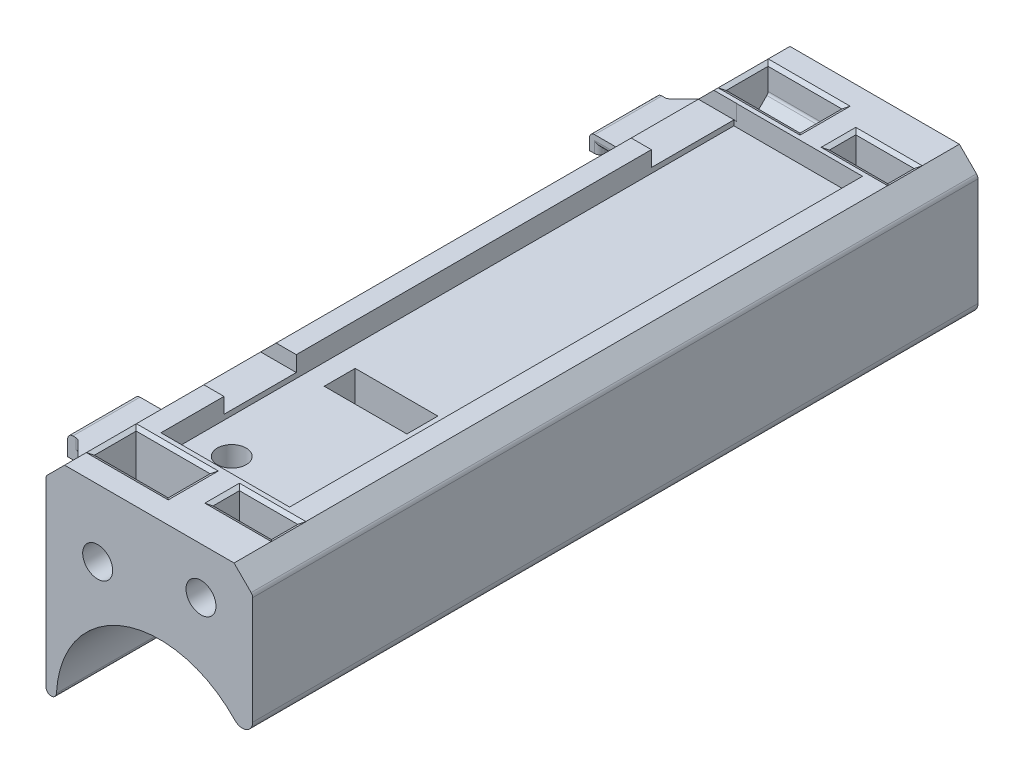
SolidWorks part; units mm, degrees
ref_plane "Front Plane" through (0, 0, 0) normal (0, 0, 1) x (1, 0, 0)
ref_plane "Top Plane" through (0, 0, 0) normal (0, 1, 0) x (1, 0, 0)
ref_plane "Right Plane" through (0, 0, 0) normal (1, 0, 0) x (0, 0, -1)
sketch "Sketch1" plane through (0, 0, 0) normal (0, 0, 1) x (1, 0, 0)
  line L0 (11, 20) -> (11, 10) construction
  line L1 (0, 0) -> (1, 0)
  line L2 (0, 0) -> (0, 20)
  line L3 (0, 20) -> (20, 20)
  line L4 (20, 4.3589) -> (20, 20)
  arc A0 (20, 4.3589) -> (1, 0) centre (11, 0) ccw
extrude "Boss-Extrude2" add sketch "Sketch1" along normal blind 35.1
sketch "Sketch2" plane through (0, 0, 0) normal (-1, 0, 0) x (0, 0, 1)
  line L0 (0, 0) -> (0, 6)
  line L1 (0, 20) -> (0, 0) construction
  line L2 (0, 6) -> (6, 6)
  line L3 (0, 0) -> (17, 0)
  line L4 (35.1, 0) -> (0, 0) construction
  line L5 (6, 6) -> (17, 0)
extrude "Cut-Extrude2" cut sketch "Sketch2" against normal blind 23.1
chamfer "Chamfer1" distance 1.8 angle 45 2 edges at (20, 20, 17.55) (0, 20, 17.55)
fillet "Fillet1" radius 20 2 edges at (0.5, 0, 17) (1.5, 6, 6)
fillet "Fillet3" radius 1 1 edges at (20, 4.3589, 22.0543)
fillet "Fillet2" radius 0.5 12 edges at (0, 18.2, 17.55) (20, 18.2, 17.55) (3, 6, 0.4501) (2.8157, 5.7461, 4.077) (1.4622, 3.0051, 11.4906) (1.0631, 1.1219, 15.4955) (1, 0, 28.5999) (0, 0, 28.5999) (0, 0.6201, 17.1581) (0, 3, 11.5) (0, 5.3799, 5.8419) (0, 6, 0.4501)
sketch "Hole Positions" plane through (0, 0, 35.1) normal (0, 0, 1) x (1, 0, 0)
  line L0 (5, 15.5) -> (11, 15.5) construction
  line L1 (11, 15.5) -> (15, 15.5) construction
  line L2 (11, 15.5) -> (11, 0) construction
  line L3 (5, 15.5) -> (5, 13.5) construction
  circle A2 centre (5, 13.5) radius 1.45
  circle A3 centre (15, 15.5) radius 1.45
  dimension "D1" = 6
  dimension "D2" = 4
  dimension "D3" = 2
  dimension "D4" = 15.5
extrude "Cut-Extrude3" cut sketch "Hole Positions" against normal blind 19
sketch "Sketch3" plane through (0, 20, 0) normal (0, 1, 0) x (1, 0, 0)
  line L1 (2.18, -28.55) -> (7.83, -28.55)
  line L2 (2.18, -28.55) -> (2.18, -31.1)
  line L3 (2.18, -31.1) -> (7.83, -31.1)
  line L4 (7.83, -28.55) -> (7.83, -31.1)
  line L5 (12.17, -28.55) -> (17.82, -28.55)
  line L6 (12.17, -28.55) -> (12.17, -31.1)
  line L7 (12.17, -31.1) -> (17.82, -31.1)
  line L8 (17.82, -28.55) -> (17.82, -31.1)
extrude "Cut-Extrude4" cut sketch "Sketch3" against normal blind 7.9
sketch "Sketch4" plane through (0, 20, 0) normal (0, 1, 0) x (1, 0, 0)
  line L1 (2.18, -31.1) -> (7.83, -31.1)
  line L2 (2.18, -31.1) -> (2.18, -28.55)
  line L3 (2.18, -28.55) -> (7.83, -28.55)
  line L4 (7.83, -31.1) -> (7.83, -28.55)
extrude "Cut-Extrude5" cut sketch "Sketch4" against normal blind 9.9
sketch "Sketch5" plane through (0, 20, 0) normal (0, 1, 0) x (1, 0, 0)
  line L1 (2.18, -28.55) -> (9.33, -28.55)
  line L2 (2.18, -28.55) -> (2.18, -32.6)
  line L3 (2.18, -32.6) -> (9.33, -32.6)
  line L4 (9.33, -28.55) -> (9.33, -32.6)
extrude "Cut-Extrude6" cut sketch "Sketch5" against normal blind 4
chamfer "Chamfer2" distance 2.6 angle 30 4 edges at (2.18, 10.1, 29.825) (7.83, 10.1, 29.825) (12.17, 12.1, 29.825) (17.82, 12.1, 29.825)
chamfer "Chamfer3" distance 1.5 angle 45 3 edges at (5.755, 16, 32.6) (9.33, 16, 30.575) (8.58, 16, 28.55)
chamfer "Chamfer4" distance 0.4 angle 30 8 edges at (14.995, 20, 31.1) (17.82, 20, 29.825) (14.995, 20, 28.55) (12.17, 20, 29.825) (9.33, 20, 30.575) (5.755, 20, 32.6) (2.18, 20, 30.575) (5.755, 20, 28.55)
fillet "Fillet5" radius 0.4 8 edges at (5.755, 17.5, 32.6) (9.33, 17.5, 30.575) (4.78, 10.1, 29.825) (5.23, 10.1, 29.825) (5.005, 16, 31.1) (7.83, 16, 29.825) (14.77, 12.1, 29.825) (15.22, 12.1, 29.825)
sketch "Sketch13" plane through (0, 0, 0) normal (0, 0, 1) x (1, 0, 0)
  line L0 (5, 13.5) -> (0, 13.5) construction
  line L1 (0, 17.9929) -> (0, 0.5) construction
  line L3 (0, 15.25) -> (-3.5, 15.25)
  line L4 (-3.5, 15.25) -> (-3.5, 11.75)
  line L6 (-3.5, 11.75) -> (0, 11.75)
  line L7 (0, 11.75) -> (0, 10.75)
  line L8 (0, 10.75) -> (-3.5, 10.75)
  line L10 (0, 15.25) -> (0, 16.25)
  line L11 (0, 16.25) -> (-3.5, 16.25)
  line L13 (-3.5, 10.75) -> (-4.5, 10.75)
  line L14 (-4.5, 10.75) -> (-4.5, 16.25)
  line L15 (-4.5, 16.25) -> (-3.5, 16.25)
extrude "Boss-Extrude3" add sketch "Sketch13" along normal blind 10 from offset 22
sketch "Sketch14" plane through (0, 10.75, 0) normal (0, -1, 0) x (1, 0, 0)
  line L5 (0, 32) -> (-3.5, 28.5)
  line L6 (-3.5, 28.5) -> (-4.5, 28.5)
  line L7 (-4.5, 32) -> (-4.5, 22) construction
  line L9 (-4.5, 28.5) -> (-4.5, 32)
  line L10 (-4.5, 32) -> (0, 32)
  dimension "D1" = 1
  dimension "D2" = 45
extrude "Cut-Extrude11" cut sketch "Sketch14" against normal blind 6
sketch "Sketch15" plane through (-4.5, 0, 0) normal (-1, 0, 0) x (0, 0, 1)
  line L12 (28.5, 13.5) -> (28.5, 14.25)
  line L13 (28.5, 16.25) -> (28.5, 10.75) construction
  line L14 (28.5, 13.5) -> (28.5, 12.75)
  line L15 (28.5, 14.25) -> (25.5, 14.25)
  line L16 (25.5, 12.75) -> (28.5, 12.75)
  line L17 (25.5, 14.25) -> (24.3724, 14.6604)
  line L18 (25.5, 12.75) -> (24.3724, 13.1604)
  line L19 (24.3724, 14.6604) -> (22, 14.6604)
  line L20 (22, 16.25) -> (22, 10.75) construction
  line L21 (22, 14.6604) -> (22, 13.1604)
  line L22 (22, 13.1604) -> (24.3724, 13.1604)
  dimension "D1" = 0.75
  dimension "D2" = 0.75
  dimension "D3" = 3
  dimension "D4" = 1.2
  dimension "D5" = 1.2
  dimension "D6" = 160
  dimension "D7" = 160
  dimension "3mm" = 3
extrude "Cut-Extrude12" cut sketch "Sketch15" against normal blind 1
fillet "Fillet6" radius 0.5 2 edges at (0, 16.25, 27) (0, 10.75, 27)
fillet "Fillet8" radius 0.5 8 edges at (-4.5, 16.25, 25.25) (-4.5, 10.75, 25.25) (-3.5, 11.25, 28.5) (-3.5, 15.75, 28.5) (-3.5, 14.9552, 22) (-1.75, 15.25, 22) (-3.5, 12.4552, 22) (-1.75, 11.75, 22)
mirror "Mirror1" about plane through (11, 0, 0) normal (0, 0, 1) of bodies 116 108
sketch "Sketch8" plane through (0, 20, 0) normal (0, 1, 0) x (1, 0, 0)
  line L0 (18.2, -28.15) -> (18.2, 28.15) construction
  line L1 (3.75, 27.725) -> (16.2, 27.725)
  line L2 (3.75, 27.725) -> (3.75, -27.725)
  line L3 (3.75, -27.725) -> (16.2, -27.725)
  line L4 (16.2, 27.725) -> (16.2, -27.725)
  line L6 (1.8, 28.15) -> (9.73, 28.15) construction
  dimension "D1" = 2
  dimension "D2" = 12.45
  dimension "D3" = 55.45
  dimension "D4" = 0.425
extrude "Cut-Extrude8" cut sketch "Sketch8" against normal blind 2 contours L2 L1 L4 L3
sketch "Sketch10" plane through (0, 0, 0) normal (-1, 0, 0) x (0, 0, 1)
  line L0 (-28.15, 20) -> (28.15, 20) construction
  line L1 (-27.7377, 20) -> (-19.7377, 20)
  line L2 (-27.7377, 20) -> (-27.7377, 18.5)
  line L3 (-27.7377, 18.5) -> (-19.7377, 18.5)
  line L4 (-19.7377, 20) -> (-19.7377, 18.5)
  line L6 (21.625, 20) -> (14.625, 20)
  line L7 (21.625, 20) -> (21.625, 18.5)
  line L8 (21.625, 18.5) -> (14.625, 18.5)
  line L9 (14.625, 20) -> (14.625, 18.5)
  dimension "D1" = 0.425
  dimension "D2" = 8
  dimension "D3" = 1.5
  dimension "D4" = 7
  dimension "D5" = 1.5
  dimension "D6" = 6.1
extrude "Cut-Extrude9" cut sketch "Sketch10" against normal blind 4
sketch "Sketch11" plane through (0, 18, 0) normal (0, 1, 0) x (1, 0, 0)
  line L0 (3.75, -27.725) -> (16.2, -27.725) construction
  line L1 (5.75, -10.925) -> (13.75, -10.925)
  line L2 (5.75, -10.925) -> (5.75, -13.925)
  line L3 (5.75, -13.925) -> (13.75, -13.925)
  line L4 (13.75, -10.925) -> (13.75, -13.925)
  line L5 (3.75, 27.725) -> (3.75, -27.725) construction
  line L6 (3.75, -21.625) -> (3.75, -27.725) construction
  circle A0 centre (7.15, -24.275) radius 1.4
  dimension "D1" = 2.8
  dimension "D2" = 3
  dimension "D3" = 8
  dimension "D4" = 3.45
  dimension "D5" = 13.8
  dimension "D6" = 2
  dimension "D7" = 3.4
extrude "Cut-Extrude10" cut sketch "Sketch11" against normal blind 3
